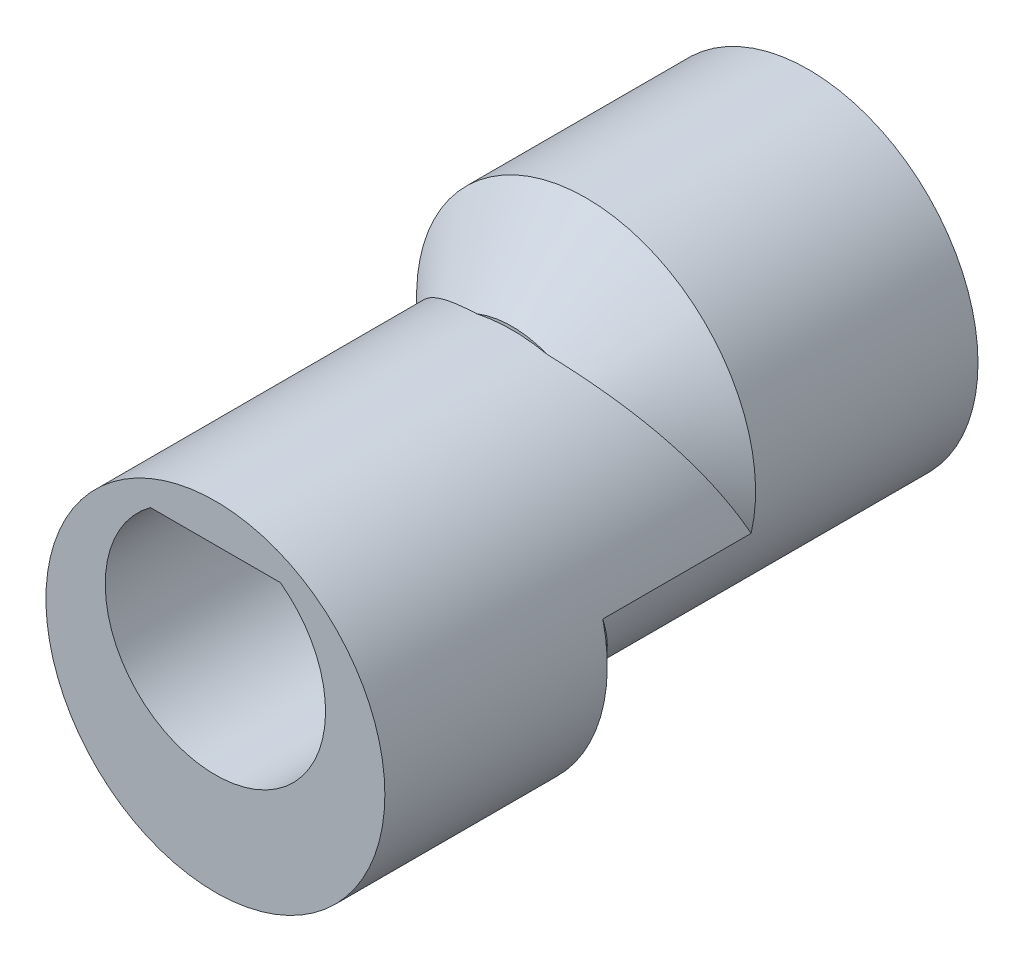
SolidWorks part; units mm, degrees
ref_plane "Plan de face" through (0, 0, 0) normal (0, 0, 1) x (1, 0, 0)
ref_plane "Plan de dessus" through (0, 0, 0) normal (0, 1, 0) x (1, 0, 0)
ref_plane "Plan de droite" through (0, 0, 0) normal (1, 0, 0) x (0, 0, -1)
sketch "Esquisse1" plane through (0, 0, 0) normal (0, 0, 1) x (1, 0, 0)
  circle A1 centre (0, 0.8221) radius 4
  dimension "D3" = 8
extrude "Boss.-Extru.1" add sketch "Esquisse1" along normal blind 7
sketch "Esquisse2" plane through (0, 0, 7) normal (0, 0, 1) x (1, 0, 0)
  circle A0 centre (0, -1) radius 4
  dimension "D1" = 8
  dimension "D2" = 1
extrude "Boss.-Extru.2" add sketch "Esquisse2" along normal blind 7
sketch "Esquisse3" plane through (0, 0, 14) normal (0, 0, 1) x (1, 0, 0)
  line L0 (-1.5, 2) -> (1.5, 2) construction
  line L1 (-1.533, 2.1) -> (1.533, 2.1)
  arc A0 (-1.5, 2) -> (1.5, 2) centre (0, 0) ccw construction
  arc A1 (-1.533, 2.1) -> (1.533, 2.1) centre (0, 0) ccw
  dimension "D1" = 5
  dimension "D2" = 2
  dimension "D3" = 0.1
extrude "Enlèv. mat.-Extru.1" cut sketch "Esquisse3" against normal through all
chamfer "Chanfrein2" distance 1.75 angle 45 1 edges at (0, 4.8221, 7)
chamfer "Chanfrein4" distance 1.75 angle 45 1 edges at (0, -5, 7)
